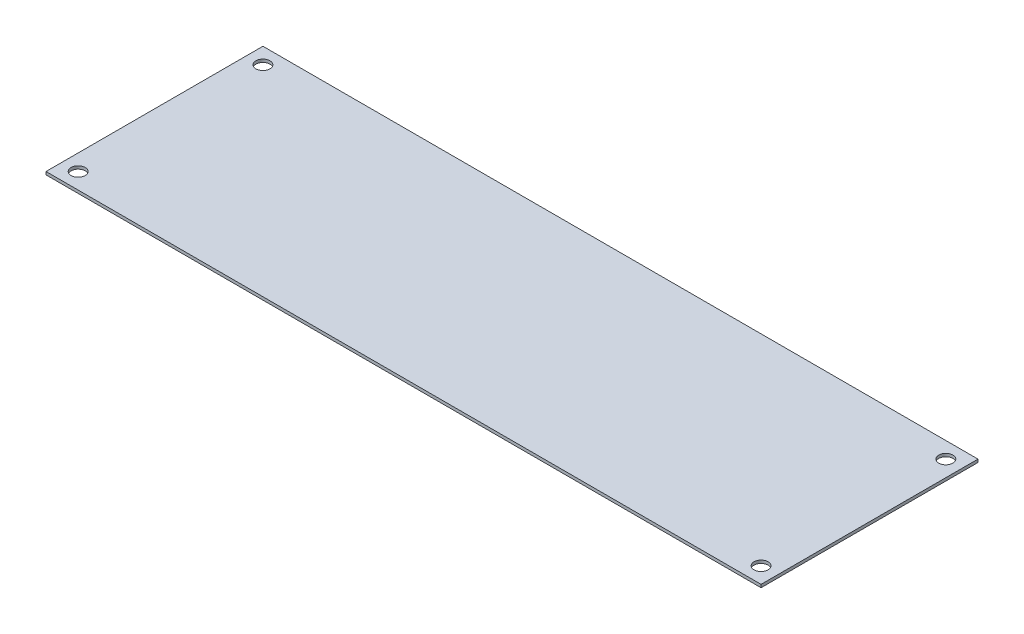
SolidWorks part; units mm, degrees
ref_plane "Front Plane" through (0, 0, 0) normal (0, 0, 1) x (1, 0, 0)
ref_plane "Top Plane" through (0, 0, 0) normal (0, 1, 0) x (1, 0, 0)
ref_plane "Right Plane" through (0, 0, 0) normal (1, 0, 0) x (0, 0, -1)
sketch "Sketch1" plane through (0, 0, 0) normal (0, 1, 0) x (1, 0, 0)
  line L1 (-89, -27) -> (89, -27)
  line L2 (-89, -27) -> (-89, 27)
  line L3 (-89, 27) -> (89, 27)
  line L4 (89, -27) -> (89, 27)
  line L5 (-89, -27) -> (89, 27) construction
  line L6 (-89, 27) -> (89, -27) construction
  circle A0 centre (85, 23) radius 1.75
  circle A1 centre (85, -23) radius 1.75
  circle A2 centre (-85, -23) radius 1.75
  circle A3 centre (-85, 23) radius 1.75
  point P0 (0, 0)
  dimension "D5" = 3.5
  dimension "D6" = 4
  dimension "D8" = 3.5
  dimension "D9" = 3.5
  dimension "D11" = 4
  dimension "D12" = 3.5
  dimension "D1" = 178
  dimension "D2" = 54
  dimension "D3" = 4
  dimension "D4" = 4
  dimension "D7" = 4
  dimension "D10" = 4
  dimension "D13" = 4
  dimension "D14" = 4
base flange "Base-Flange1" sketch "Sketch1" thickness 0.7366 reverse thickness direction no parameters "D1"=0.7366
sketch "Bend-Lines1" plane through (0, 0, 0) normal (0, 1, 0) x (1, 0, 0)
sketch "Bounding-Box1" plane through (0, 0, 0) normal (0, 1, 0) x (1, 0, 0)
sheet metal parameters "Sheet-Metal1" thickness 0.7366 parameters "D1"=0.7366
flat pattern "Flat-Pattern1" [suppressed]
sketch "Bend-Lines2" plane through (0, 0, 0) normal (0, 1, 0) x (1, 0, 0)
sketch "Bounding-Box2" [suppressed] plane through (0, 0, 0) normal (0, 1, 0) x (1, 0, 0)
